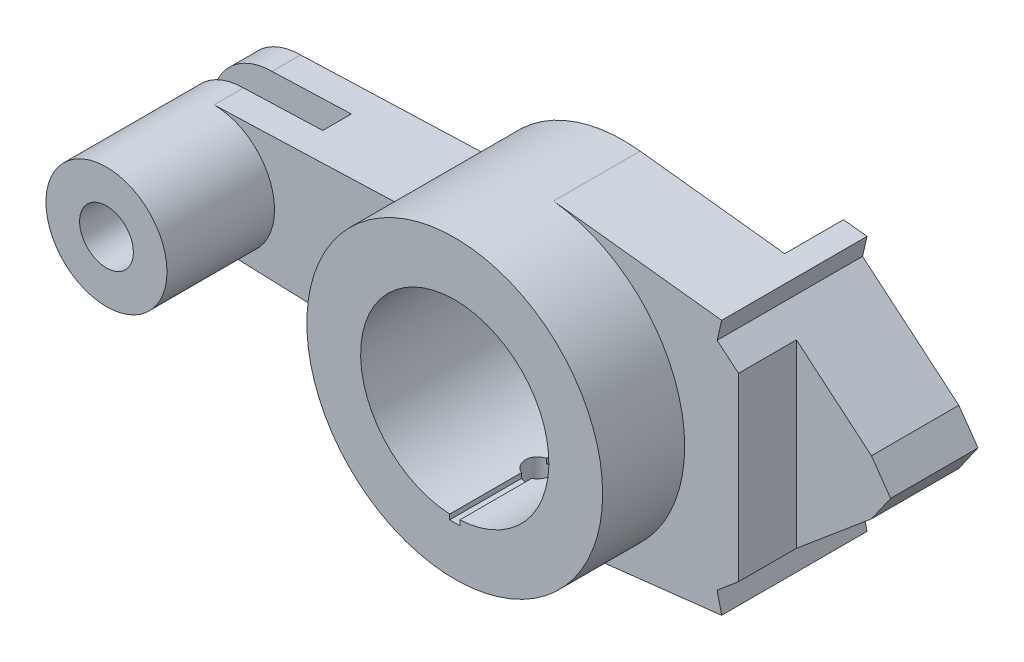
SolidWorks part; units mm, degrees
ref_plane "Front Plane" through (0, 0, 0) normal (0, 0, 1) x (1, 0, 0)
ref_plane "Top Plane" through (0, 0, 0) normal (0, 1, 0) x (1, 0, 0)
ref_plane "Right Plane" through (0, 0, 0) normal (1, 0, 0) x (0, 0, -1)
sketch "Sketch1" plane through (0, 0, 0) normal (0, 0, 1) x (1, 0, 0)
  line L0 (-76.2, -14.2875) -> (-31.1085, -15.875)
  line L1 (34.925, 0) -> (73.025, 0) construction
  line L2 (69.85, 0) -> (65.3272, 6.4592)
  line L3 (3.9661, 34.6991) -> (43.6562, 30.1625)
  line L4 (73.025, 0) -> (42.5888, 25.539) construction
  line L5 (65.3272, 6.4592) -> (42.5888, 25.539)
  line L6 (43.6562, 30.1625) -> (42.5888, 25.539)
  line L7 (69.85, 0) -> (65.3272, -6.4592)
  line L8 (65.3272, -6.4592) -> (42.5888, -25.539)
  line L9 (43.6562, -30.1625) -> (42.5888, -25.539)
  line L10 (3.9661, -34.6991) -> (43.6562, -30.1625)
  line L11 (-31.1085, -15.875) -> (-31.1085, 15.875) construction
  line L12 (-31.1085, 15.875) -> (-76.2, 14.2875)
  line L13 (-55.5625, 15.0141) -> (-55.5625, -15.0141)
  line L14 (38.1, 30.7976) -> (38.1, -30.7976)
  line L15 (47.625, 21.3131) -> (47.625, -21.3131)
  circle A0 centre (0, 0) radius 34.925
  circle A1 centre (-76.2, 0) radius 14.2875
  circle A2 centre (-76.2, 0) radius 6.35
  circle A3 centre (0, 0) radius 22.225
  point P20 (-31.1085, 0)
  dimension "D1" = 28.575
  dimension "D2" = 69.85
  dimension "D3" = 12.7
  dimension "D4" = 44.45
  dimension "D6" = 20.6375
  dimension "D14" = 43.6562
  dimension "D13" = 31.75
  dimension "D7" = 73.025
  dimension "D5" = 76.2
  dimension "D8" = 30.1625
  dimension "D9" = 40
  dimension "D10" = 55
  dimension "D11" = 117
  dimension "D12" = 3.175
  dimension "D15" = 38.1
  dimension "D16" = 22.225
extrude "Boss-Extrude7" add sketch "Sketch1" against normal blind 20.6375 contours L3 L14 L10 L9 L8 L7 L2 L5 L6 | L5 L15 L8 L7 L2 region at (42.5131, 0, 0) region at (55.5676, 0, 0)
extrude "Boss-Extrude10" add sketch "Sketch1<18>" against normal blind 6.7469 contours A0 L10 L14 L3 | A0 L12 L13 L0 | A1 L0 L13 L12 | A1 A2 | A0 A3 region at (-60.8966, 0, 0) region at (-90.0834, 0, 0) region at (-44.5051, 0, 0) region at (-33.9372, 0, 0) region at (26.6373, -23.7661, 0)
sketch "Sketch1<18>" plane through (0, 0, 0) normal (0, 0, 1) x (1, 0, 0) same geometry as "Sketch1"
extrude "Boss-Extrude11" add sketch "Sketch1<20>" along normal blind 6.7469 contours A0 A3 | A0 L10 L14 L3 | L15 L5 L6 L3 L14 L10 L9 L8 | A0 L12 L13 L0 | A1 L0 L13 L12 region at (-60.8966, 0, 0) region at (-44.5051, 0, 0) region at (-33.9372, 0, 0) region at (26.6373, -23.7661, 0) region at (42.5131, 0, 0)
sketch "Sketch1<20>" plane through (0, 0, 0) normal (0, 0, 1) x (1, 0, 0) same geometry as "Sketch1"
extrude "Boss-Extrude12" add sketch "Sketch1<21>" along normal blind 6.9453 from vertex contours A1 A2 | A1 L0 L13 L12 | A0 L12 L13 L0 | A0 A3 | A0 L10 L14 L3 | L15 L5 L6 L3 L14 L10 L9 L8 region at (-60.8966, 0, 0) region at (-90.0834, 0, 0) region at (-44.5051, 0, 0) region at (-33.9372, 0, 0) region at (26.6373, -23.7661, 0) region at (42.5131, 0, 0) starting at point (-76.2, 14.2875, 6.7469)
sketch "Sketch1<21>" plane through (0, 0, 0) normal (0, 0, 1) x (1, 0, 0) same geometry as "Sketch1"
extrude "Boss-Extrude13" add sketch "Sketch1<22>" along normal blind 25.4 from vertex contours A1 A2 region at (-90.0834, 0, 0) starting at point (-76.2, 14.2875, 13.6922)
sketch "Sketch1<22>" plane through (0, 0, 0) normal (0, 0, 1) x (1, 0, 0) same geometry as "Sketch1"
extrude "Boss-Extrude14" add sketch "Sketch1<23>" along normal blind 19.3675 from vertex contours A0 A3 region at (-33.9372, 0, 0) starting at point (3.9661, 34.6991, 13.6922)
sketch "Sketch1<23>" plane through (0, 0, 0) normal (0, 0, 1) x (1, 0, 0) same geometry as "Sketch1"
sketch "Sketch4" plane through (0, 0, 33.0597) normal (0, 0, 1) x (1, 0, 0)
  line L0 (0, -22.225) -> (0, -34.925) construction
  line L1 (-1.1906, -22.1931) -> (-1.1906, -23.3837)
  line L2 (-1.1906, -23.3837) -> (1.1906, -23.3837)
  line L3 (1.1906, -23.3837) -> (1.1906, -22.1931)
  circle A0 centre (0, 0) radius 22.225 construction
  circle A1 centre (0, 0) radius 34.925 construction
  circle A2 centre (0, 0) radius 22.225
  point P12 (0, -23.3837)
  circle M3 centre (0, 0) radius 22.225
  dimension "D1" = 1.1906
  dimension "D2" = 2.3813
extrude "Cut-Extrude3" cut sketch "Sketch4" against normal through all contours L0 A2 L1 L2 | L0 L2 L3 M3 region at (0.598, -22.799, 33.0597) region at (-0.598, -22.799, 33.0597)
sketch "Sketch5" plane through (0, 0, 0) normal (0, 1, 0) x (1, 0, 0)
  line L0 (0, -33.0597) -> (0, 6.7469) construction
  line L1 (-1.1906, -33.0597) -> (1.1906, -33.0597) construction
  line L2 (3.9661, 6.7469) -> (-31.1085, 6.7469) construction
  circle A0 centre (0, -13.1564) radius 3.175
  point P9 (0, -13.1564)
  dimension "D1" = 6.35
extrude "Cut-Extrude4" cut sketch "Sketch5" against normal through all
sketch "Sketch6" plane through (0, 0, 0) normal (0, 1, 0) x (1, 0, 0)
  line L0 (-69.85, -6.7469) -> (-82.55, -6.7469) construction
  line L1 (-90.4875, 0) -> (-57.4675, 0)
  line L2 (-90.4875, 0) -> (-90.4875, -6.7469)
  line L3 (-90.4875, -6.7469) -> (-57.4675, -6.7469)
  line L4 (-57.4675, 0) -> (-57.4675, -6.7469)
  dimension "D1" = 33.02
extrude "Cut-Extrude5" cut sketch "Sketch6" against normal through all both and the other way through all
